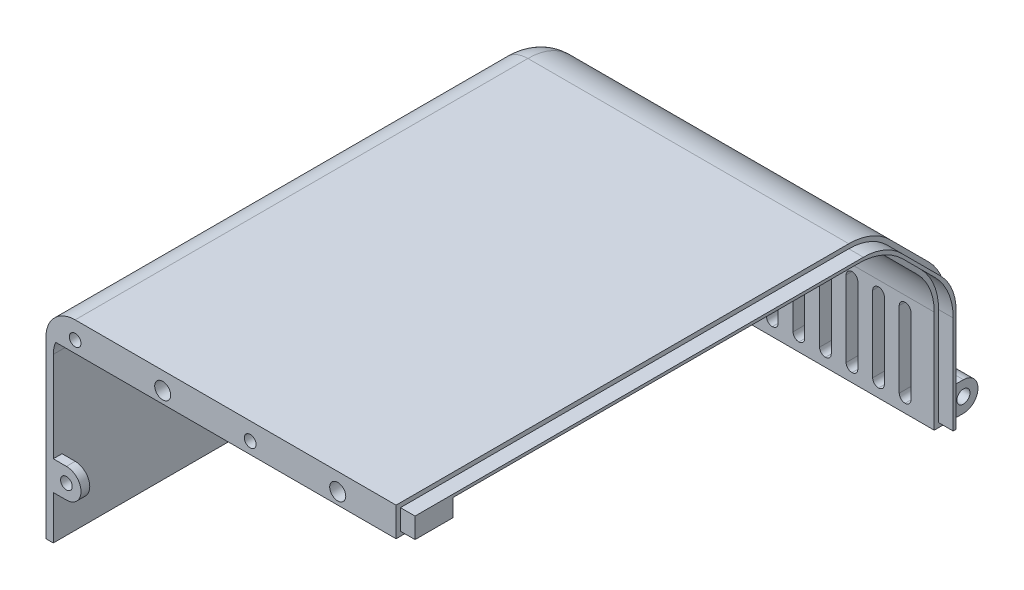
SolidWorks part; units mm, degrees
ref_plane "Alzado" through (0, 0, 0) normal (0, 0, 1) x (1, 0, 0)
ref_plane "Planta" through (0, 0, 0) normal (0, 1, 0) x (1, 0, 0)
ref_plane "Vista lateral" through (0, 0, 0) normal (1, 0, 0) x (0, 0, -1)
sketch "Croquis1" plane through (0, 0, 0) normal (1, 0, 0) x (0, 0, -1)
  line L0 (-210, 0) -> (210, 0)
  line L2 (21.5278, 70) -> (185, 70)
  line L3 (-210, 0) -> (-210, 20)
  line L4 (-210, 20) -> (-109.6319, 150.4846)
  line L5 (210, 0) -> (210, 45)
  line L6 (210, 45) -> (185, 70)
  line L7 (21.5278, 70) -> (21.5278, 75)
  line L8 (21.5278, 75) -> (-28.7753, 148.2935)
  arc A0 (-28.7753, 148.2935) -> (-109.6319, 150.4846) centre (-70, 120) ccw
  circle A1 centre (-70, 120) radius 13
  arc A3 (-109.6319, 150.4846) -> (-28.7753, 148.2935) centre (-70, 120) ccw construction
  point P3 (0, 0)
  dimension "D4" = 100
  dimension "D5" = 26
  dimension "D1" = 420
  dimension "D2" = 120
  dimension "D3" = 70
  dimension "D6" = 20
  dimension "D7" = 70
  dimension "D8" = 45
  dimension "D9" = 50.3031
  dimension "D10" = 45
  dimension "D11" = 5
extrude "Saliente-Extruir1" add sketch "Croquis1" along normal blind 120
sketch "Croquis2" plane through (120, 0, 0) normal (1, 0, 0) x (0, 0, -1)
  line L2 (210, 45) -> (185, 70) construction
  line L3 (37.5278, 60) -> (37.5278, 66)
  line L4 (37.5278, 66) -> (183.3431, 66)
  line L5 (185, 70) -> (21.5278, 70) construction
  line L7 (210, 0) -> (210, 45) construction
  line L8 (-206, 0) -> (-206, 18.6396)
  line L9 (-210, 0) -> (210, 0) construction
  line L20 (-206, 18.6396) -> (-106.4613, 148.0459)
  line L21 (-109.6319, 150.4846) -> (-210, 20) construction
  line L22 (-210, 20) -> (-210, 0) construction
  line L23 (-32.0733, 146.03) -> (17.5278, 73.7594)
  line L24 (17.5278, 73.7594) -> (17.5278, 60)
  line L28 (17.5278, 60) -> (37.5278, 60)
  line L29 (183.3431, 66) -> (206, 43.3431)
  line L33 (206, 43.3431) -> (206, 0)
  line L34 (206, 0) -> (-206, 0)
  line L35 (21.5278, 70) -> (21.5278, 75) construction
  arc A8 (-32.0733, 146.03) -> (-106.4613, 148.0459) centre (-70, 120) ccw
  arc A9 (-32.0733, 146.03) -> (-106.4613, 148.0459) centre (-70, 120) ccw
  dimension "D2" = 4
  dimension "D3" = 4
  dimension "D4" = 4
  dimension "D5" = 4
  dimension "D6" = 4
  dimension "D7" = 10
  dimension "D8" = 20
  dimension "D1" = 4
extrude "Cortar-Extruir1" cut sketch "Croquis2" against normal offset from surface (117.5 mm away) 2.5 up to face at (0, 66.5967, -10.0229)
fillet "Redondeo1" radius 20 6 edges at (60, 45, -210) (60, 70, -185) (60, 20, 210) (61.25, 66, -183.3431) (61.25, 43.3431, -206) (61.25, 18.6396, 206)
sketch "Croquis3" plane through (0, 0, -21.5278) normal (0, 0, -1) x (-1, 0, 0)
  line L0 (0, 64.1421) -> (-120, 64.1421) construction
  line L1 (-185, 189.1421) -> (65, 189.1421)
  line L2 (-185, 189.1421) -> (-185, -60.8579)
  line L3 (-185, -60.8579) -> (65, -60.8579)
  line L4 (65, 189.1421) -> (65, -60.8579)
  line L5 (-185, 189.1421) -> (65, -60.8579) construction
  line L6 (-185, -60.8579) -> (65, 189.1421) construction
  point P0 (-60, 64.1421)
  dimension "D1" = 250
  dimension "D2" = 250
extrude "Cortar-Extruir2" cut sketch "Croquis3" against normal through all
sketch "Croquis4" plane through (0, 0, -21.5278) normal (0, 0, 1) x (1, 0, 0)
  line L0 (120, 60) -> (2.5, 60) construction
  circle A0 centre (40, 64) radius 2.75
  circle A1 centre (100, 64) radius 2.75
  circle A3 centre (10, 64) radius 2
  circle A4 centre (70, 64) radius 2
  dimension "D1" = 5.5
  dimension "D2" = 5.5
  dimension "D4" = 4
  dimension "D6" = 4
  dimension "D7" = 4
  dimension "D3" = 60
  dimension "D5" = 40
  dimension "D9" = 30
  dimension "D10" = 30
extrude "Cortar-Extruir3" cut sketch "Croquis4" against normal blind 6
fillet "Redondeo2" radius 10 10 edges at (0, 18.3579, -210) (0, 44.3694, -208.4776) (0, 57.5, -197.5) (0, 68.4776, -184.3694) (0, 70, -99.1218) (2.5, 17.5294, -206) (2.5, 42.7125, -204.4776) (2.5, 54.6716, -194.6716) (2.5, 64.4776, -182.7125) (2.5, 66, -106.2933)
sketch "Croquis7" plane through (120, 0, 0) normal (1, 0, 0) x (0, 0, -1)
  line L20 (23.0278, 68.5) -> (23.0278, 61.5)
  line L21 (23.0278, 61.5) -> (36.0278, 61.5)
  line L22 (36.0278, 61.5) -> (36.0278, 67.5)
  line L23 (36.0278, 67.5) -> (175.0589, 67.5)
  line L24 (190.2617, 61.2028) -> (201.2028, 50.2617)
  line L25 (207.5, 35.0589) -> (207.5, 1.5)
  line L26 (207.5, 1.5) -> (208.5, 1.5)
  line L27 (208.5, 1.5) -> (208.5, 36.7157)
  line L28 (203.0815, 49.7972) -> (189.7972, 63.0815)
  line L29 (176.7157, 68.5) -> (23.0278, 68.5)
  line L40 (23.0278, 68.5) -> (23.0278, 61.5)
  line L41 (23.0278, 61.5) -> (36.0278, 61.5)
  line L42 (36.0278, 61.5) -> (36.0278, 67.5)
  line L43 (36.0278, 67.5) -> (175.0589, 67.5)
  line L44 (190.2617, 61.2028) -> (201.2028, 50.2617)
  line L45 (207.5, 35.0589) -> (207.5, 1.5)
  line L46 (207.5, 1.5) -> (208.5, 1.5)
  line L47 (208.5, 1.5) -> (208.5, 36.7157)
  line L48 (203.0815, 49.7972) -> (189.7972, 63.0815)
  line L49 (176.7157, 68.5) -> (23.0278, 68.5)
  arc A8 (190.2617, 61.2028) -> (175.0589, 67.5) centre (175.0589, 46) ccw
  arc A9 (207.5, 35.0589) -> (201.2028, 50.2617) centre (186, 35.0589) ccw
  arc A10 (208.5, 36.7157) -> (203.0815, 49.7972) centre (190, 36.7157) ccw
  arc A11 (189.7972, 63.0815) -> (176.7157, 68.5) centre (176.7157, 50) ccw
  arc A16 (190.2617, 61.2028) -> (175.0589, 67.5) centre (175.0589, 46) ccw
  arc A17 (207.5, 35.0589) -> (201.2028, 50.2617) centre (186, 35.0589) ccw
  arc A18 (208.5, 36.7157) -> (203.0815, 49.7972) centre (190, 36.7157) ccw
  arc A19 (189.7972, 63.0815) -> (176.7157, 68.5) centre (176.7157, 50) ccw
  dimension "D1" = 1.5
extrude "Saliente-Extruir2" add sketch "Croquis7" along normal blind 5
sketch "Croquis8" plane through (0, 0, -210) normal (0, 0, -1) x (-1, 0, 0)
  line L1 (-112, 33) -> (-108, 33)
  line L2 (-112, 33) -> (-112, 3)
  line L3 (-112, 3) -> (-108, 3)
  line L4 (-108, 33) -> (-108, 3)
  line L5 (-112, 33) -> (-108, 3) construction
  line L6 (-112, 3) -> (-108, 33) construction
  line L7 (-120, 0) -> (-10, 0) construction
  line L8 (-102.9, 33) -> (-102.9, 3)
  line L9 (-102.9, 33) -> (-98.9, 33)
  line L10 (-98.9, 33) -> (-98.9, 3)
  line L11 (-102.9, 3) -> (-98.9, 3)
  line L12 (-93.8, 33) -> (-93.8, 3)
  line L13 (-93.8, 33) -> (-89.8, 33)
  line L14 (-89.8, 33) -> (-89.8, 3)
  line L15 (-93.8, 3) -> (-89.8, 3)
  line L16 (-84.7, 33) -> (-84.7, 3)
  line L17 (-84.7, 33) -> (-80.7, 33)
  line L18 (-80.7, 33) -> (-80.7, 3)
  line L19 (-84.7, 3) -> (-80.7, 3)
  line L20 (-75.6, 33) -> (-75.6, 3)
  line L21 (-75.6, 33) -> (-71.6, 33)
  line L22 (-71.6, 33) -> (-71.6, 3)
  line L23 (-75.6, 3) -> (-71.6, 3)
  line L24 (-66.5, 33) -> (-66.5, 3)
  line L25 (-66.5, 33) -> (-62.5, 33)
  line L26 (-62.5, 33) -> (-62.5, 3)
  line L27 (-66.5, 3) -> (-62.5, 3)
  line L28 (-57.4, 33) -> (-57.4, 3)
  line L29 (-57.4, 33) -> (-53.4, 33)
  line L30 (-53.4, 33) -> (-53.4, 3)
  line L31 (-57.4, 3) -> (-53.4, 3)
  line L32 (-48.3, 33) -> (-48.3, 3)
  line L33 (-48.3, 33) -> (-44.3, 33)
  line L34 (-44.3, 33) -> (-44.3, 3)
  line L35 (-48.3, 3) -> (-44.3, 3)
  line L36 (-39.2, 33) -> (-39.2, 3)
  line L37 (-39.2, 33) -> (-35.2, 33)
  line L38 (-35.2, 33) -> (-35.2, 3)
  line L39 (-39.2, 3) -> (-35.2, 3)
  line L40 (-30.1, 33) -> (-30.1, 3)
  line L41 (-30.1, 33) -> (-26.1, 33)
  line L42 (-26.1, 33) -> (-26.1, 3)
  line L43 (-30.1, 3) -> (-26.1, 3)
  line L44 (-21, 33) -> (-21, 3)
  line L45 (-21, 33) -> (-17, 33)
  line L46 (-17, 33) -> (-17, 3)
  line L47 (-21, 3) -> (-17, 3)
  line L48 (-120, 1.5) -> (-120, 36.7157) construction
  point P0 (-110, 18)
  dimension "D1" = 4
  dimension "D2" = 30
  dimension "D3" = 10
  dimension "D4" = 18
  dimension "D6" = 95
  dimension "D5" = 11
extrude "Cortar-Extruir4" cut sketch "Croquis8" against normal blind 10
fillet "Redondeo3" radius 2 44 edges at (21, 33, -208) (17, 33, -208) (17, 3, -208) (21, 3, -208) (30.1, 33, -208) (26.1, 33, -208) (26.1, 3, -208) (30.1, 3, -208) (39.2, 33, -208) (35.2, 33, -208) (35.2, 3, -208) (39.2, 3, -208) (48.3, 33, -208) (44.3, 33, -208) (44.3, 3, -208) (48.3, 3, -208) (57.4, 33, -208) (53.4, 33, -208) (53.4, 3, -208) (57.4, 3, -208) (66.5, 33, -208) (62.5, 33, -208) (62.5, 3, -208) (66.5, 3, -208) (75.6, 33, -208) (71.6, 33, -208) (71.6, 3, -208) (75.6, 3, -208) (84.7, 33, -208) (80.7, 33, -208) (80.7, 3, -208) (84.7, 3, -208) (93.8, 33, -208) (89.8, 33, -208) (89.8, 3, -208) (93.8, 3, -208) (102.9, 33, -208) (98.9, 33, -208) (98.9, 3, -208) (102.9, 3, -208) (112, 3, -208) (112, 33, -208) (108, 3, -208) (108, 33, -208)
sketch "Croquis9" plane through (0, 66, 0) normal (0, -1, 0) x (1, 0, 0)
  text T0 "<b>BY: Marcos Gabriel Urraca</b>" font "Coolvetica" height 3.5
extrude "Cortar-Extruir5" cut sketch "Croquis9" against normal blind 2
sketch "Croquis10" plane through (0, 0, 0) normal (0, -1, 0) x (1, 0, 0)
  line L0 (2.5, -125) -> (5, -125)
  line L1 (2.5, -37.5278) -> (2.5, -175.0589) construction
  line L2 (5, -135) -> (2.5, -135)
  line L3 (2.5, -135) -> (2.5, -125)
  line L4 (0, -21.5278) -> (0, -200) construction
  circle A0 centre (5, -130) radius 2.25
  arc A1 (5, -125) -> (5, -135) centre (5, -130) cw
  dimension "D1" = 4.5
  dimension "D2" = 10
  dimension "D3" = 5
  dimension "D4" = 130
extrude "Saliente-Extruir3" add sketch "Croquis10" against normal blind 6
sketch "Croquis11" plane through (120, 0, 0) normal (1, 0, 0) x (0, 0, -1)
  line L0 (210, 10) -> (216, 10)
  line L1 (210, 0) -> (210, 36.7157) construction
  line L2 (216, 0) -> (210, 0)
  line L3 (210, 0) -> (210, 10)
  line L4 (206, 35.0589) -> (206, 0) construction
  line L5 (206, 0) -> (210, 0) construction
  arc A0 (216, 10) -> (216, 0) centre (216, 5) cw
  circle A1 centre (216, 5) radius 2.25
  dimension "D3" = 4.5
  dimension "D1" = 10
  dimension "D2" = 10
extrude "Saliente-Extruir4" add sketch "Croquis11" against normal blind 6
sketch "Croquis12" plane through (0, 0, -21.5278) normal (0, 0, 1) x (1, 0, 0)
  line L0 (2.5, 15) -> (7, 15)
  line L1 (2.5, 35.0589) -> (2.5, 0) construction
  line L2 (7, 25) -> (2.5, 25)
  line L3 (2.5, 25) -> (2.5, 15)
  line L4 (0, 0) -> (0, 60) construction
  arc A0 (7, 15) -> (7, 25) centre (7, 20) ccw
  circle A1 centre (7, 20) radius 2
  dimension "D1" = 4
  dimension "D2" = 10
  dimension "D3" = 7
  dimension "D4" = 20
extrude "Saliente-Extruir5" add sketch "Croquis12" against normal blind 3
